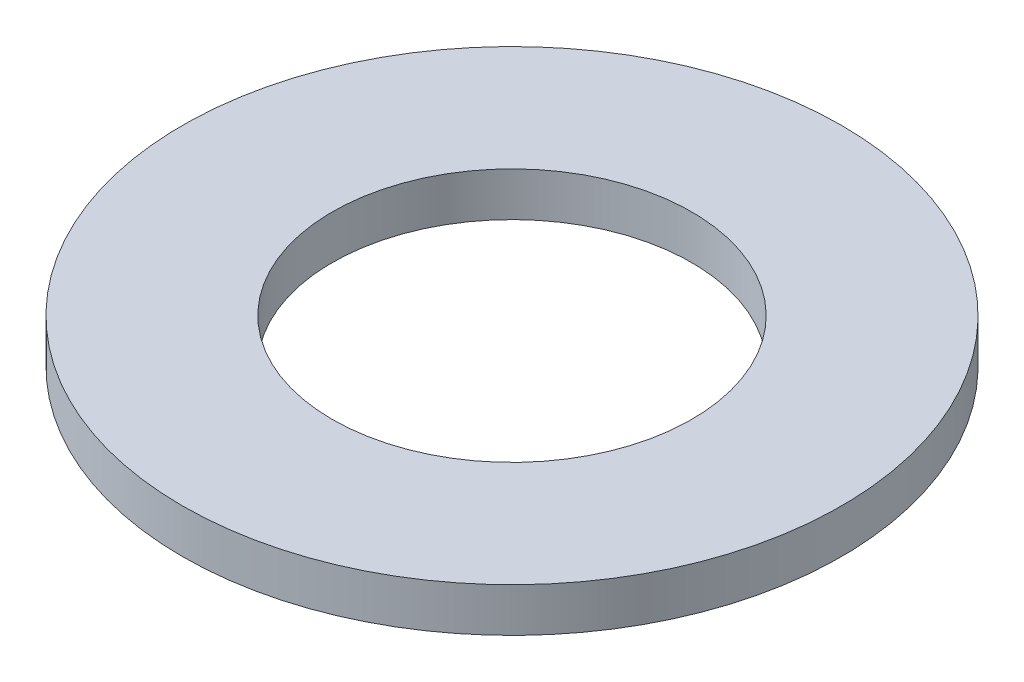
SolidWorks part; units mm, degrees
ref_plane "Front Plane" through (0, 0, 0) normal (0, 0, 1) x (1, 0, 0)
ref_plane "Top Plane" through (0, 0, 0) normal (0, 1, 0) x (1, 0, 0)
ref_plane "Right Plane" through (0, 0, 0) normal (1, 0, 0) x (0, 0, -1)
sketch "Sketch1" plane through (0, 0, 0) normal (0, 1, 0) x (1, 0, 0)
  circle A0 centre (0, 0) radius 82.5
  dimension "FLANGE_OD" = 165
extrude "Boss-Extrude1" add sketch "Sketch1" along normal blind 11
sketch "Sketch2" plane through (0, 0, 0) normal (0, 1, 0) x (1, 0, 0)
  circle A0 centre (0, 0) radius 45
  dimension "BORE_D" = 90
extrude "Cut-Extrude1" cut sketch "Sketch2" along normal through all
sketch "Sketch3" plane through (0, 11, 0) normal (0, 1, 0) x (1, 0, 0)
  circle A0 centre (0, 0) radius 37.7323 construction
  circle A1 centre (-37.7323, 0) radius 2.9676
  dimension "BOLT_D" = 5.9351
  dimension "BOLT_PCD" = 75.4645
extrude "Cut-Extrude2" cut sketch "Sketch3" against normal blind 7.2152 rebuild error yes
pattern_circular "CirPattern1" count 3 over 360 rebuild error yes
